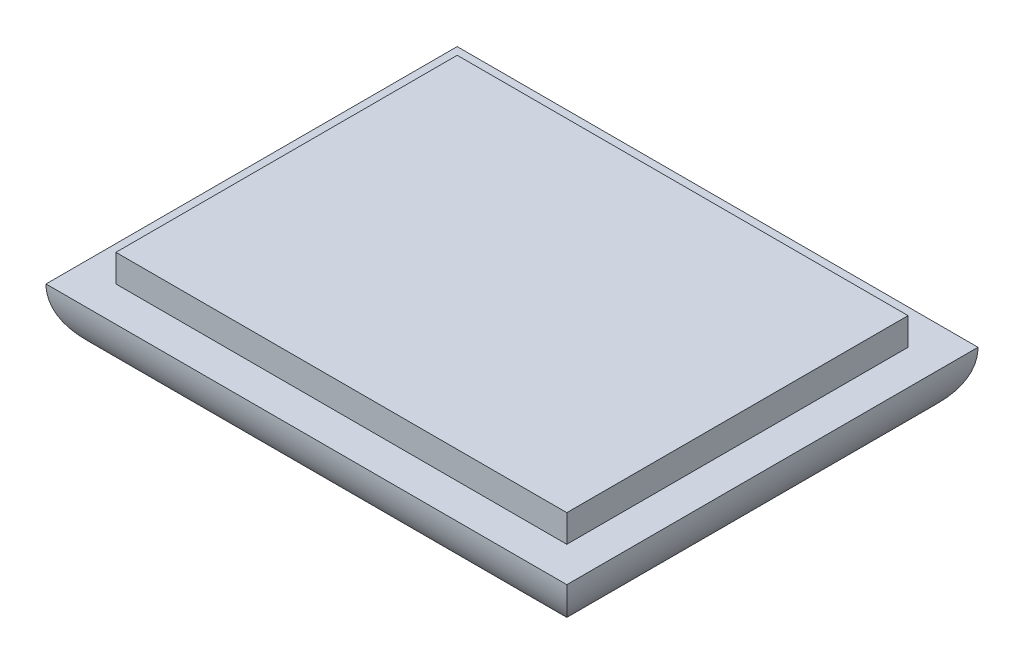
SolidWorks part; units mm, degrees
material "ONYX"
ref_plane "Front Plane" through (0, 0, 0) normal (0, 0, 1) x (1, 0, 0)
ref_plane "Top Plane" through (0, 0, 0) normal (0, 1, 0) x (1, 0, 0)
ref_plane "Right Plane" through (0, 0, 0) normal (1, 0, 0) x (0, 0, -1)
sketch "Sketch1" plane through (0, 0, 0) normal (0, 1, 0) x (1, 0, 0)
  line L1 (16.5, -12.5) -> (-16.5, -12.5) construction
  line L2 (16.5, -12.5) -> (16.5, 12.5) construction
  line L3 (16.5, 12.5) -> (-16.5, 12.5) construction
  line L4 (-16.5, -12.5) -> (-16.5, 12.5) construction
  line L5 (16.5, -12.5) -> (-16.5, 12.5) construction
  line L6 (16.5, 12.5) -> (-16.5, -12.5) construction
  line L7 (19, -15) -> (-19, -15)
  line L8 (19, -15) -> (19, 15)
  line L9 (19, 15) -> (-19, 15)
  line L10 (-19, -15) -> (-19, 15)
  line L11 (19, -15) -> (-19, 15) construction
  line L12 (19, 15) -> (-19, -15) construction
  point P0 (0, 0)
  point P6 (0, 0)
  dimension "D1" = 33
  dimension "D2" = 25
  dimension "D3" = 2.5
  dimension "D4" = 2.5
extrude "Boss-Extrude1" add sketch "Sketch1" along normal blind 5 contours L2 L1 L4 L3 | L8 L7 L10 L9
sketch "Sketch2" plane through (0, 5, 0) normal (0, 1, 0) x (1, 0, 0)
  line L1 (16.45, -12.45) -> (-16.45, -12.45)
  line L2 (16.45, -12.45) -> (16.45, 12.45)
  line L3 (16.45, 12.45) -> (-16.45, 12.45)
  line L4 (-16.45, -12.45) -> (-16.45, 12.45)
  line L5 (16.45, -12.45) -> (-16.45, 12.45) construction
  line L6 (16.45, 12.45) -> (-16.45, -12.45) construction
  point P0 (0, 0)
  dimension "D1" = 32.9
  dimension "D2" = 24.9
extrude "Boss-Extrude2" add sketch "Sketch2" along normal blind 2
fillet "Fillet1" radius 5 4 edges at (-19, 0, 0) (0, 0, 15) (19, 0, 0) (0, 0, -15)
